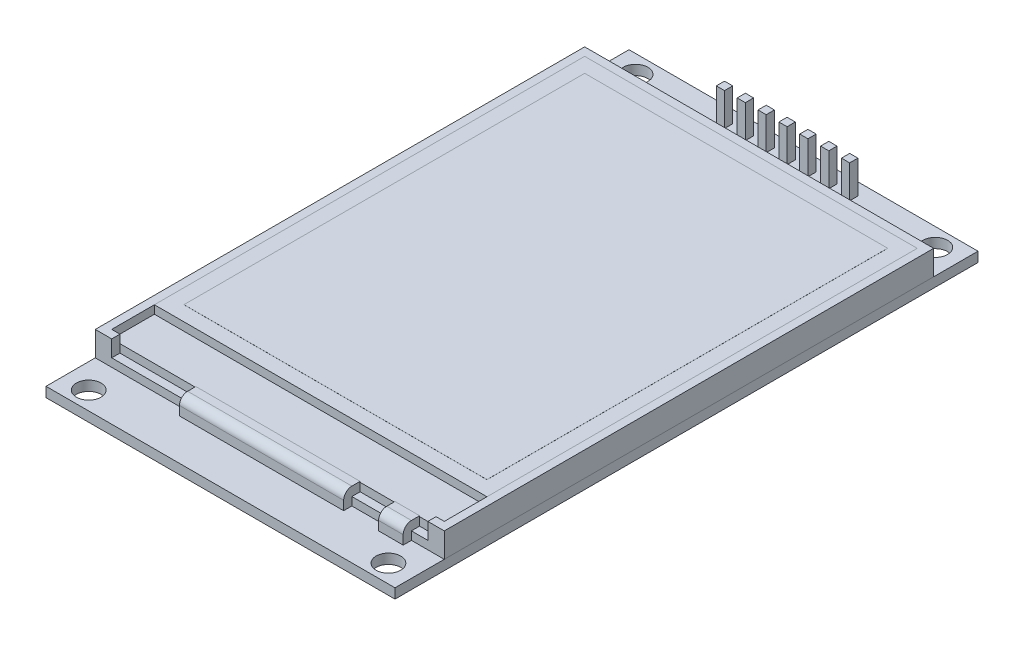
SolidWorks part; units mm, degrees
material "ABS"
ref_plane "Front Plane" through (0, 0, 0) normal (0, 0, 1) x (1, 0, 0)
ref_plane "Top Plane" through (0, 0, 0) normal (0, 1, 0) x (1, 0, 0)
ref_plane "Right Plane" through (0, 0, 0) normal (1, 0, 0) x (0, 0, -1)
sketch "Sketch1" plane through (0, 0, 0) normal (0, 1, 0) x (1, 0, 0)
  line L1 (-21.25, 35.5) -> (21.25, 35.5)
  line L2 (-21.25, 35.5) -> (-21.25, -35.5)
  line L3 (-21.25, -35.5) -> (21.25, -35.5)
  line L4 (21.25, 35.5) -> (21.25, -35.5)
  line L5 (0, -35.5) -> (0, 35.5) construction
  line L6 (-21.25, 0) -> (21.25, 0) construction
  point P0 (0, 0)
  dimension "D1" = 42.5
  dimension "D2" = 71
extrude "Boss-Extrude1" add sketch "Sketch1" along normal blind 1.2
sketch "Sketch7" plane through (0, 1.2, 0) normal (0, 1, 0) x (1, 0, 0)
  line L0 (-21.25, 35.5) -> (21.25, 35.5) construction
  line L1 (-21.25, 35.5) -> (-21.25, -35.5) construction
  circle A0 centre (-18.25, 33.3) radius 1.5
  dimension "D1" = 3
  dimension "D2" = 2.2
  dimension "D3" = 3
extrude "Cut-Extrude2" cut sketch "Sketch7" against normal through all
mirror "Mirror1" about plane through (0, 0, 0) normal (0, 0, 1) of "Cut-Extrude2" second plane through (0, 0, 0) second plane normal (1, 0, 0)
sketch "Sketch8" plane through (0, 1.2, 0) normal (0, 1, 0) x (1, 0, 0)
  line L0 (0, -10.821) -> (0, 10.821) construction
  line L1 (-0.5, 34) -> (0.5, 34)
  line L2 (-0.5, 34) -> (-0.5, 33)
  line L3 (-0.5, 33) -> (0.5, 33)
  line L4 (0.5, 34) -> (0.5, 33)
  line L5 (0, 33) -> (0, 34) construction
  line L6 (-0.5, 33.5) -> (0.5, 33.5) construction
  line L7 (-21.25, 35.5) -> (21.25, 35.5) construction
  point P0 (0, 33.5)
  dimension "D1" = 2
  dimension "D2" = 1
extrude "Boss-Extrude5" add sketch "Sketch8" along normal blind 4 and the other way blind 8
pattern_linear "LPattern1" count 4 spacing 2.54 along (1, 0, 0) count 4 spacing 2.54 along (-1, 0, 0) of "Boss-Extrude5" pattern seed only yes
sketch "Sketch10" plane through (0, 0, 0) normal (0, -1, 0) x (1, 0, 0)
  line L0 (-21.25, -35.5) -> (-21.25, 35.5) construction
  line L1 (-12.75, -24.5) -> (-3.85, -24.5)
  line L2 (-12.75, -24.5) -> (-12.75, -6.5)
  line L3 (-12.75, -6.5) -> (-3.85, -6.5)
  line L4 (-3.85, -24.5) -> (-3.85, -6.5)
  line L5 (-21.25, -35.5) -> (21.25, -35.5) construction
  dimension "D1" = 8.5
  dimension "D2" = 11
  dimension "D3" = 18
  dimension "D4" = 8.9
extrude "PCB components" add sketch "Sketch10" along normal blind 1.8 separate body
sketch "Sketch2" plane through (0, 1.2, 0) normal (0, 1, 0) x (1, 0, 0)
  line L1 (-21.25, 30.1) -> (21.25, 30.1)
  line L2 (-21.25, 30.1) -> (-21.25, -29.5)
  line L3 (-21.25, -29.5) -> (21.25, -29.5)
  line L4 (21.25, 30.1) -> (21.25, -29.5)
  line L6 (-21.25, 35.5) -> (-21.25, -35.5) construction
  line L7 (21.25, 35.5) -> (21.25, -35.5) construction
  line L8 (-21.25, 35.5) -> (21.25, 35.5) construction
  line L9 (-21.25, -35.5) -> (21.25, -35.5) construction
  line L10 (-21.25, 0.3) -> (21.25, 0.3) construction
  point P4 (0, 0.3)
  dimension "D1" = 5.4
  dimension "D2" = 6
extrude "Boss-Extrude2" add sketch "Sketch2" along normal blind 3 separate body
sketch "Sketch3" plane through (0, 4.2, 0) normal (0, 1, 0) x (1, 0, 0)
  line L1 (-20.25, 29.1) -> (20.25, 29.1)
  line L2 (-20.25, 29.1) -> (-20.25, -28.5)
  line L3 (-20.25, -28.5) -> (20.25, -28.5)
  line L4 (20.25, 29.1) -> (20.25, -28.5)
  line L5 (0, -10.821) -> (0, 10.821) construction
  line L6 (-21.25, 30.1) -> (21.25, 30.1) construction
  line L7 (-21.25, 35.5) -> (-21.25, -35.5) construction
  line L9 (-21.25, 0.3) -> (21.25, 0.3) construction
  point P8 (0, 29.1)
  point P12 (-20.25, 0.3)
  dimension "D1" = 1
  dimension "D2" = 1
extrude "Cut-Extrude1" cut sketch "Sketch3" against normal through all
sketch "Sketch12" plane through (0, 0, 29.5) normal (0, 0, 1) x (1, 0, 0)
  line L0 (0, -10.821) -> (0, 10.821) construction
  line L1 (-19.25, 4.2) -> (19.25, 4.2)
  line L2 (-19.25, 4.2) -> (-19.25, 2.2)
  line L3 (-19.25, 2.2) -> (19.25, 2.2)
  line L4 (19.25, 4.2) -> (19.25, 2.2)
  line L5 (-21.25, 4.2) -> (21.25, 4.2) construction
  line L6 (-21.25, 1.2) -> (21.25, 1.2) construction
  point P4 (0, 4.2)
  dimension "D1" = 2
  dimension "D2" = 1
extrude "Cut-Extrude4" cut sketch "Sketch12" against normal up to surface (1 mm away) up to face at (0, 2.7, 28.5)
sketch "Sketch5" plane through (0, 1.2, 0) normal (0, 1, 0) x (1, 0, 0)
  line L4 (20.25, 29.1) -> (-20.25, 29.1)
  line L5 (20.25, -28.5) -> (20.25, 29.1)
  line L6 (-20.25, -28.5) -> (20.25, -28.5)
  line L7 (-20.25, 29.1) -> (-20.25, -28.5)
  line L8 (20.25, 29.1) -> (-20.25, 29.1)
  line L9 (20.25, -28.5) -> (20.25, 29.1)
  line L10 (-20.25, -28.5) -> (20.25, -28.5)
  line L11 (-20.25, 29.1) -> (-20.25, -28.5)
  dimension "D1" = 0
extrude "Boss-Extrude3" add sketch "Sketch5" along normal up to surface (3 mm away) separate body up to face at (0, 4.2, 9.4667)
sketch "Sketch9" plane through (0, 4.2, 0) normal (0, 1, 0) x (1, 0, 0)
  line L0 (20.25, 29.1) -> (20.25, -28.5) construction
  line L1 (-20.25, -28.5) -> (20.25, -28.5)
  line L2 (-20.25, -28.5) -> (-20.25, -23.3)
  line L3 (-20.25, -23.3) -> (20.25, -23.3)
  line L4 (20.25, -28.5) -> (20.25, -23.3)
  line L5 (-21.25, -29.5) -> (21.25, -29.5) construction
  dimension "D1" = 6.2
extrude "Cut-Extrude3" cut sketch "Sketch9" against normal blind 1
sketch "Sketch6" plane through (0, 4.2, 0) normal (0, 1, 0) x (1, 0, 0)
  line L0 (0, -10.821) -> (0, 10.821) construction
  line L1 (-18.45, 27.3) -> (18.45, 27.3)
  line L2 (-18.45, 27.3) -> (-18.45, -21.5)
  line L3 (-18.45, -21.5) -> (18.45, -21.5)
  line L4 (18.45, 27.3) -> (18.45, -21.5)
  line L5 (21.25, 35.5) -> (-21.25, 35.5) construction
  line L6 (-20.25, 29.1) -> (20.25, 29.1) construction
  line L7 (-20.25, 29.1) -> (-20.25, -28.5) construction
  line L12 (20.25, 29.1) -> (-20.25, 29.1) construction
  line L13 (-20.25, 29.1) -> (-20.25, -28.5) construction
  line L14 (-21.25, 35.5) -> (-21.25, -35.5) construction
  line L15 (-20.25, -23.3) -> (20.25, -23.3) construction
  line L16 (20.25, -23.3) -> (-20.25, -23.3) construction
  line L17 (-21.25, -35.5) -> (21.25, -35.5) construction
  point P4 (0, 27.3)
  dimension "D1" = 1.8
  dimension "D2" = 1.8
  dimension "D3" = 1.8
  dimension "D4" = 12.2
  dimension "D7" = 6.4
  dimension "D8" = 1
extrude "Boss-Extrude4" add sketch "Sketch6" along normal blind 0.01
sketch "Sketch11" plane through (0, 1.2, 0) normal (0, 1, 0) x (1, 0, 0)
  line L0 (0, -10.821) -> (0, 10.821) construction
  line L1 (-10, -30.5) -> (10, -30.5)
  line L2 (-10, -30.5) -> (-10, -28.5)
  line L3 (-10, -28.5) -> (10, -28.5)
  line L4 (10, -30.5) -> (10, -28.5)
  line L5 (-20.25, -28.5) -> (20.25, -28.5) construction
  line L6 (-21.25, -29.5) -> (21.25, -29.5) construction
  line L7 (21.25, 35.5) -> (21.25, -35.5) construction
  line L8 (14.25, -28.5) -> (17.25, -28.5)
  line L9 (14.25, -28.5) -> (14.25, -30.5)
  line L10 (14.25, -30.5) -> (17.25, -30.5)
  line L11 (17.25, -28.5) -> (17.25, -30.5)
  point P4 (0, -28.5)
  dimension "D1" = 1
  dimension "D2" = 20
  dimension "D3" = 3
  dimension "D4" = 4
extrude "Boss-Extrude7" add sketch "Sketch11" along normal offset from surface (2.1 mm away) 0.1 separate body up to face at (0, 3.2, 25.9) offset beyond the face yes
fillet "Fillet1" radius 1 1 edges at (0, 3.3, 30.5)
fillet "Fillet2" radius 1 1 edges at (15.75, 3.3, 30.5)
